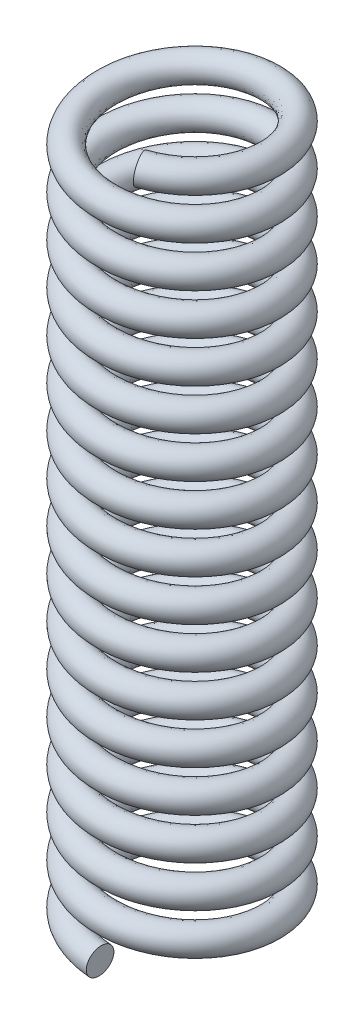
SolidWorks part; units mm, degrees
note: '?' marks a value the reader was unsure of.
ref_plane "Front Plane" through (0, 0, 0) normal (0, 0, 1) x (1, 0, 0)
ref_plane "Top Plane" through (0, 0, 0) normal (0, 1, 0) x (1, 0, 0)
ref_plane "Right Plane" through (0, 0, 0) normal (1, 0, 0) x (0, 0, -1)
sketch "Sketch1" plane through (0, 0, 0) normal (0, 1, 0) x (1, 0, 0)
  circle A0 centre (0, 0) radius 11.9
  dimension "D1" = 23.8
curve "Helix/Spiral1" pitch 6 height 101.6 turns 16.9333
ref_plane "Plane1" through (4.8402, 101.6, 10.8712) normal (-0.9106, 0.08, 0.4054) x (0.3322, -0.4418, 0.8333)
sketch "Sketch2" plane through (4.8402, 101.6, 10.8712) normal (-0.9106, 0.08, 0.4054) x (0.3322, -0.4418, 0.8333)
  circle A0 centre (0, 0) radius 2
  dimension "D1" = 4
sweep "Sweep1" add profiles "Sketch2" path "Helix/Spiral1"
sketch "Sketch3" plane through (0, 0, 0) normal (0, 1, 0) x (1, 0, 0)
  point P0 (0, 0)
ref_plane "Plane2" through (0, 110, 0) normal (0, 1, 0) x (1, 0, 0)
sketch "Sketch4" plane through (0, 110, 0) normal (0, 1, 0) x (1, 0, 0)
  point P0 (0, 0)
ref_axis "Axis1" through (0, 110, 0) along (0, -1, 0)?
